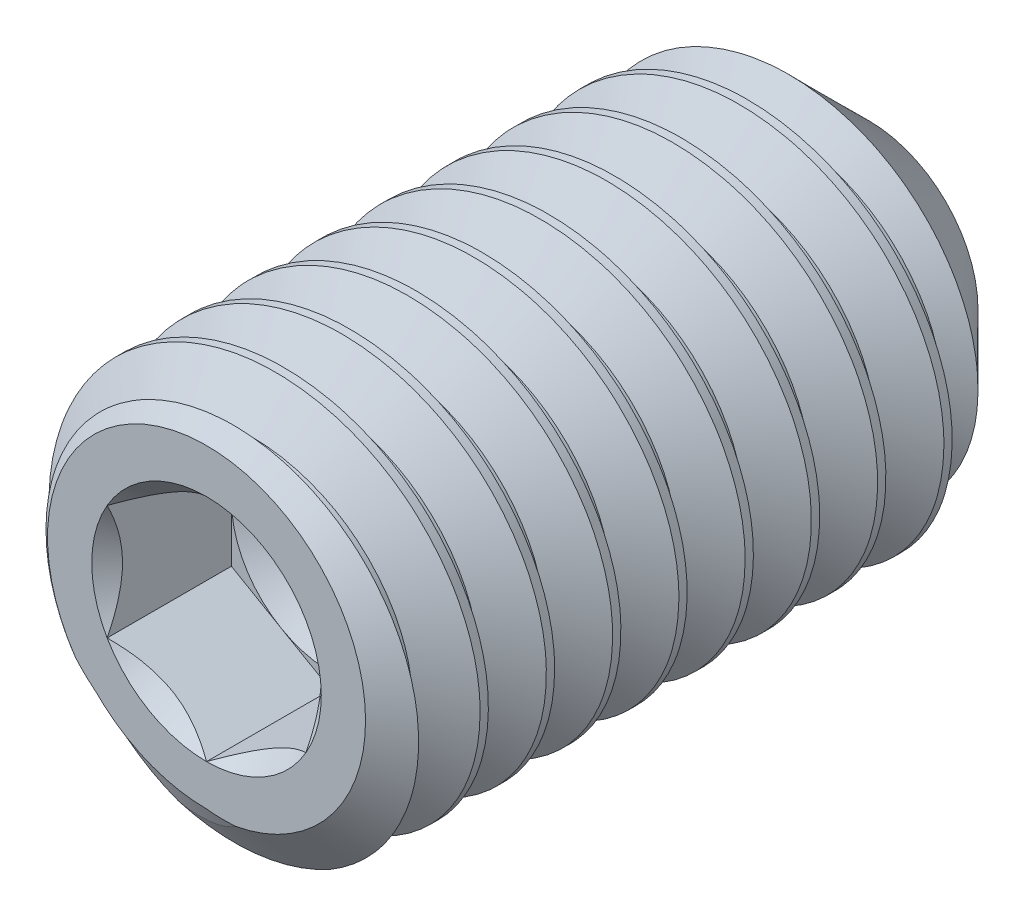
SolidWorks part; units mm, degrees
ref_plane "Front" through (0, 0, 0) normal (0, 0, 1) x (1, 0, 0)
ref_plane "Top" through (0, 0, 0) normal (0, 1, 0) x (1, 0, 0)
ref_plane "Right" through (0, 0, 0) normal (1, 0, 0) x (0, 0, -1)
sketch "Sketch22" plane through (0, 0, 0) normal (1, 0, 0) x (0, 0, -1)
  line L0 (-4.5061, 0) -> (-4.5061, 2.4)
  line L1 (-4.5061, 2.4) -> (-4.086, 3)
  line L2 (-4.086, 3) -> (4.1378, 3)
  line L3 (4.1378, 3) -> (5.4939, 1.6439)
  line L4 (5.4939, 1.6439) -> (4.5061, 0)
  line L5 (4.5061, 0) -> (-4.5061, 0)
  line L6 (4.5061, 0) -> (5.4939, 0) construction
  line L7 (5.4939, 0) -> (5.4939, 1.6439) construction
  line L8 (5.4939, -1.6439) -> (4.5061, 0) construction
  line L9 (-4.086, -3) -> (4.1378, -3) construction
  dimension "Dia" = 6
  dimension "Length" = 10
  dimension "D3" = 35
  dimension "D5" = 118
  dimension "D6" = 45
  dimension "D7" = 4.8
revolve "Revolve1" add sketch "Sketch22" angle 360 about L6
ref_plane "Plane1" through (0, 0, -5.4939) normal (0, 0, 1) x (1, 0, 0)
sketch "Sketch27" plane through (0, 0, -5.4939) normal (0, 0, 1) x (1, 0, 0)
  circle A0 centre (0, 0) radius 3 construction
  circle A1 centre (0, 0) radius 3
curve "Helix/Spiral1" pitch 1 height 11 radius 3 centre (0, 0, -5.4939) axis (0, 0, 1) start towards (0, 1, 0)
sketch "Sketch28" plane through (0, 0, 0) normal (1, 0, 0) x (0, 0, -1)
  line L0 (5.4939, 3) -> (6.3689, 3)
  line L1 (6.3689, 3) -> (5.9939, 2.3505)
  line L2 (5.9939, 2.3505) -> (5.8689, 2.3505)
  line L3 (5.8689, 2.3505) -> (5.4939, 3)
  line L4 (5.6814, 2.6752) -> (6.1814, 2.6752) construction
  line L6 (-4.086, 3) -> (4.1378, 3) construction
  dimension "D1" = 0.125
  dimension "D3" = 60
  dimension "D2" = 0.5
sweep "Cut-Sweep2" cut profiles "Sketch28" path "Helix/Spiral1"
sketch "Sketch23" plane through (0, 0, 4.5061) normal (0, 0, 1) x (1, 0, 0)
  line L1 (0, 1.7321) -> (-1.5, 0.866)
  line L2 (-1.5, 0.866) -> (-1.5, -0.866)
  line L3 (-1.5, -0.866) -> (0, -1.7321)
  line L4 (0, -1.7321) -> (1.5, -0.866)
  line L5 (1.5, -0.866) -> (1.5, 0.866)
  line L6 (1.5, 0.866) -> (0, 1.7321)
  circle A0 centre (0, 0) radius 1.5 construction
  dimension "Hex" = 3
extrude "Cut-Extrude10" cut sketch "Sketch23" against normal blind 1.875
sketch "Sketch24" plane through (0, 0, 4.5061) normal (0, 0, 1) x (1, 0, 0)
  circle A0 centre (0, 0) radius 1.7321
extrude "Cut-Extrude11" cut sketch "Sketch24" against normal through all draft 45
sketch "Sketch26" plane through (0, 0, 2.6311) normal (0, 0, 1) x (1, 0, 0)
  circle A0 centre (0, 0) radius 1.5 construction
  circle A1 centre (0, 0) radius 1.5
extrude "Cut-Extrude12" cut sketch "Sketch26" against normal through all draft 60
sketch "Sketch30" plane through (0, 0, 0) normal (1, 0, 0) x (0, 0, -1)
  line L0 (-4.086, 3) -> (4.1378, 3) construction
  line L1 (-4.5061, 0) -> (-4.5061, 2.4) construction
  line L2 (5.4939, 0) -> (5.4939, 1.6439) construction
  line L3 (-4.086, -3) -> (4.1378, -3) construction
  point P0 (-4.5061, 3)
  point P1 (5.4939, 3)
  point P2 (5.4939, -3)
  point P11 (3.9939, -3)
  dimension "D1" = 1.5
sketch "Sketch31" plane through (0, 0, 0) normal (1, 0, 0) x (0, 0, -1)
  line L2 (4.5061, 0) -> (5.4939, -1.6439)
  line L3 (5.4939, 1.6439) -> (4.5061, 0)
equation "\"D7@Sketch22\"=\"Dia@Sketch22\"*.8"
equation "\"D1@Sketch28\" = \"D4@Helix/Spiral1\" * .125"
equation "\"D2@Sketch28\" = \"D4@Helix/Spiral1\" * .5"
equation "\"D3@Helix/Spiral1\" = \"Length@Sketch22\" + \"D4@Helix/Spiral1\""
equation "\"D1@Sketch30\" = \"D4@Helix/Spiral1\" * 1.5"
equation "\"hex Depth@Cut-Extrude10\" = \"Hex@Sketch23\" * .625"
